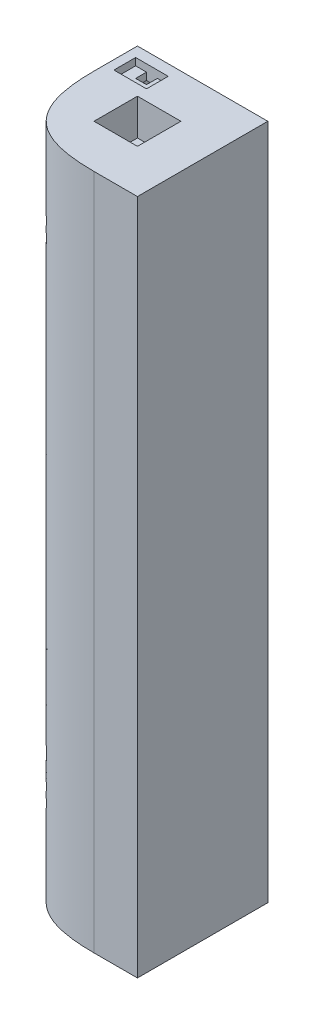
SolidWorks part; units mm, degrees
ref_plane "Front Plane" through (0, 0, 0) normal (0, 0, 1) x (1, 0, 0)
ref_plane "Top Plane" through (0, 0, 0) normal (0, 1, 0) x (1, 0, 0)
ref_plane "Right Plane" through (0, 0, 0) normal (1, 0, 0) x (0, 0, -1)
sketch "Sketch1" plane through (0, 0, 0) normal (0, 1, 0) x (1, 0, 0)
  line L1 (0, 0) -> (36, 0)
  line L2 (0, 0) -> (0, 36)
  line L3 (0, 36) -> (36, 36)
  line L4 (36, 0) -> (36, 36)
  dimension "D1" = 36
  dimension "D2" = 36
extrude "Boss-Extrude1" add sketch "Sketch1" along normal blind 186.9
fillet "Fillet1" radius 24 1 edges at (0, 93.45, 0) conic rho 0.55
sketch "Sketch2" plane through (0, 0, 0) normal (0, -1, 0) x (1, 0, 0)
  line L0 (36, -36) -> (0, -36) construction
  line L2 (36, 0) -> (36, -36) construction
  line L3 (24, 0) -> (36, 0) construction
  circle A0 centre (18, -18) radius 2
  dimension "D1" = 4
  dimension "D2" = 18
  dimension "D3" = 18
extrude "Cut-Extrude1" cut sketch "Sketch2" against normal blind 5
sketch "Sketch3" plane through (0, 0, 0) normal (0, -1, 0) x (1, 0, 0)
  line L0 (36, 0) -> (36, -36) construction
  line L1 (26.2, -5) -> (31, -5)
  line L2 (26.2, -5) -> (26.2, -26.2)
  line L3 (26, -31) -> (31, -31)
  line L4 (31, -5) -> (31, -31)
  line L5 (24, 0) -> (36, 0) construction
  line L6 (36, -36) -> (0, -36) construction
  line L7 (0, -36) -> (0, -24) construction
  line L8 (5, -31) -> (26, -31)
  line L9 (5, -31) -> (5, -26.2)
  line L10 (5, -26.2) -> (26.2, -26.2)
  line L13 (9.4, -9.4) -> (14.2, -9.4)
  line L14 (9.4, -9.4) -> (9.4, -14.2)
  line L15 (9.4, -14.2) -> (14.2, -14.2)
  line L16 (14.2, -9.4) -> (14.2, -14.2)
  dimension "D7" = 4.8
  dimension "D8" = 4.8
  dimension "D9" = 12
  dimension "D1" = 5
  dimension "D2" = 5
  dimension "D3" = 5
  dimension "D4" = 5
  dimension "D5" = 4.8
  dimension "D6" = 4.8
  dimension "D10" = 12
  dimension "D11" = 9.4
  dimension "D12" = 9.4
extrude "Boss-Extrude2" add sketch "Sketch3" along normal blind 4
sketch "Sketch4" plane through (0, 0, -36) normal (0, 0, -1) x (-1, 0, 0)
  line L0 (0, 186.9) -> (0, 0) construction
  line L1 (-10, 182.9) -> (-4, 182.9)
  line L2 (-10, 182.9) -> (-10, 178.9)
  line L3 (-10, 178.9) -> (-4, 178.9)
  line L4 (-4, 182.9) -> (-4, 178.9)
  line L5 (-36, 186.9) -> (0, 186.9) construction
  line L6 (-36, 186.9) -> (-36, 0) construction
  line L7 (-32, 182.9) -> (-26, 182.9)
  line L8 (-32, 182.9) -> (-32, 178.9)
  line L9 (-32, 178.9) -> (-26, 178.9)
  line L10 (-26, 182.9) -> (-26, 178.9)
  line L12 (-10, 162.9) -> (-4, 162.9)
  line L13 (-10, 162.9) -> (-10, 158.9)
  line L14 (-10, 158.9) -> (-4, 158.9)
  line L15 (-4, 162.9) -> (-4, 158.9)
  dimension "D1" = 4
  dimension "D2" = 4
  dimension "D3" = 4
  dimension "D4" = 6
  dimension "D5" = 6
  dimension "D6" = 4
  dimension "D7" = 4
  dimension "D8" = 4
  dimension "D9" = 16
  dimension "D10" = 4
extrude "Cut-Extrude2" cut sketch "Sketch4" against normal blind 9
sketch "Sketch5" plane through (0, 186.9, 0) normal (0, 1, 0) x (1, 0, 0)
  line L0 (0, 36) -> (0, 24) construction
  line L1 (5.5, 33) -> (8.5, 33)
  line L2 (5.5, 33) -> (5.5, 30)
  line L3 (5.5, 30) -> (8.5, 30)
  line L4 (8.5, 33) -> (8.5, 30)
  line L5 (36, 36) -> (0, 36) construction
  line L6 (24, 0) -> (36, 0) construction
  line L7 (12, 12) -> (24, 12)
  line L8 (12, 12) -> (12, 24)
  line L9 (12, 24) -> (24, 24)
  line L10 (24, 12) -> (24, 24)
  dimension "D1" = 3
  dimension "D2" = 3
  dimension "D3" = 5.5
  dimension "D4" = 3
  dimension "D5" = 12
  dimension "D6" = 12
  dimension "D7" = 12
  dimension "D8" = 12
extrude "Cut-Extrude3" cut sketch "Sketch5" against normal blind 10
sketch "Sketch6" plane through (0, 186.9, 0) normal (0, 1, 0) x (1, 0, 0)
  line L0 (5.5, 33) -> (5.5, 30) construction
  line L1 (2.5, 33) -> (11.5, 33)
  line L2 (2.5, 33) -> (2.5, 27)
  line L3 (2.5, 27) -> (11.5, 27)
  line L4 (11.5, 33) -> (11.5, 27)
  line L5 (8.5, 30) -> (8.5, 33) construction
  line L6 (8.5, 33) -> (5.5, 33) construction
  line L7 (5.5, 30) -> (8.5, 30) construction
  dimension "D1" = 3
  dimension "D2" = 3
  dimension "D3" = 0
  dimension "D4" = 3
extrude "Cut-Extrude4" cut sketch "Sketch6" against normal blind 2
